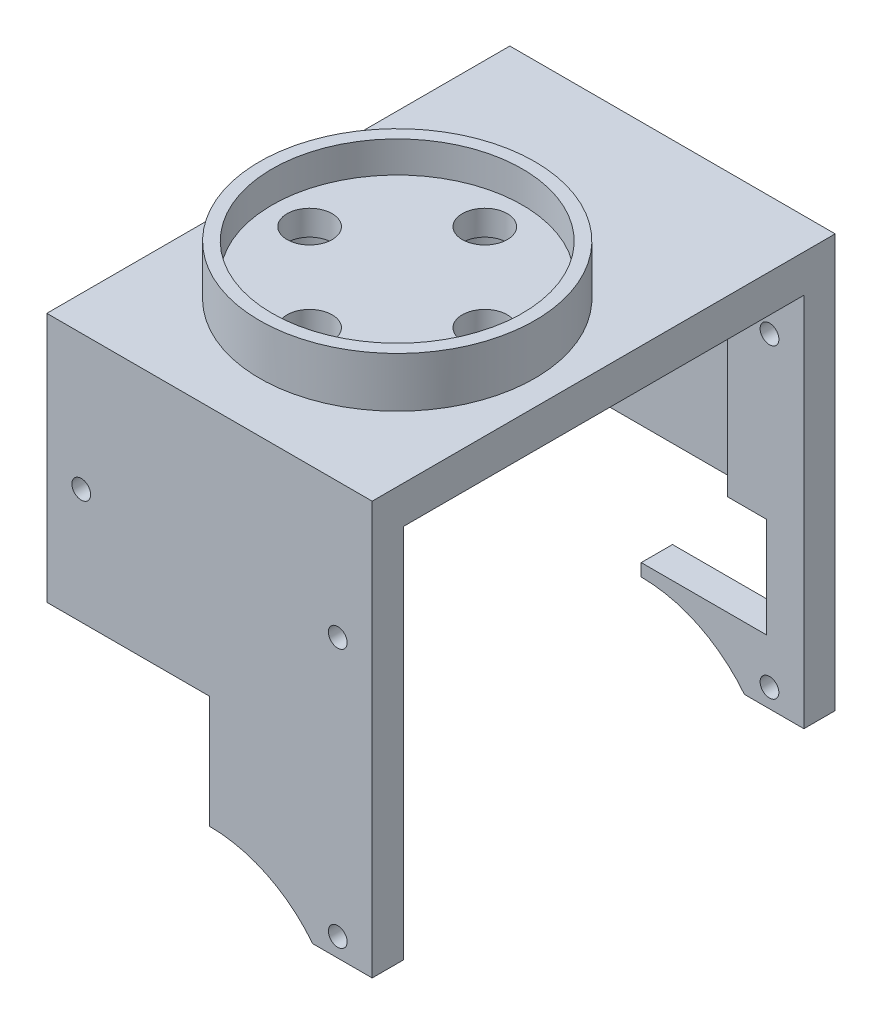
SolidWorks part; units mm, degrees
ref_plane "前视基准面" through (0, 0, 0) normal (0, 0, 1) x (1, 0, 0)
ref_plane "上视基准面" through (0, 0, 0) normal (0, 1, 0) x (1, 0, 0)
ref_plane "右视基准面" through (0, 0, 0) normal (1, 0, 0) x (0, 0, -1)
other "Configuration Table"
sketch "草图1" plane through (0, 0, 0) normal (0, 0, 1) x (1, 0, 0)
  line L1 (0, 0) -> (26, 0)
  line L2 (0, 0) -> (0, 33)
  line L3 (0, 33) -> (26, 33)
  line L4 (26, 0) -> (26, 33)
  dimension "D1" = 26
  dimension "D2" = 33
extrude "凸台-拉伸1" add sketch "草图1" along normal blind 37
sketch "草图3" plane through (0, 0, 0) normal (0, -1, 0) x (1, 0, 0)
  line L0 (0, 18.5) -> (-50000, 18.5) construction
  line L1 (0, 37) -> (0, 0) construction
  line L2 (26, 37) -> (26, 0) construction
  line L3 (0, 34.5) -> (26, 34.5)
  line L4 (0, 34.5) -> (0, 2.5)
  line L5 (0, 2.5) -> (26, 2.5)
  line L6 (26, 34.5) -> (26, 2.5)
  point P4 (0, 18.5)
  point P9 (0, 18.5)
  dimension "D1" = 32
extrude "切除-拉伸1" cut sketch "草图3" against normal offset from surface (30 mm away) 3 up to face at (13, 33, 18.5)
sketch "草图2" plane through (0, 0, 37) normal (0, 0, 1) x (1, 0, 0)
  line L0 (13, 0) -> (13, -50000) construction
  line L1 (0, 0) -> (26, 0) construction
  line L3 (2.75, 22.2) -> (23.25, 22.2) construction
  line L4 (2.75, 22.2) -> (2.75, 1.5) construction
  line L5 (2.75, 1.5) -> (23.25, 1.5) construction
  line L6 (23.25, 22.2) -> (23.25, 1.5) construction
  circle A0 centre (2.75, 1.5) radius 0.75
  circle A1 centre (23.25, 1.5) radius 0.75
  circle A2 centre (23.25, 22.2) radius 0.75
  circle A3 centre (2.75, 22.2) radius 0.75
  point P4 (13, 0)
  point P9 (13, 22.2)
  dimension "D4" = 1.5
  dimension "D5" = 1.5
  dimension "D6" = 1.5
  dimension "D7" = 1.5
  dimension "D1" = 1.5
  dimension "D2" = 20.5
  dimension "D3" = 20.7
extrude "切除-拉伸2" cut sketch "草图2" against normal up to next and the other way through all
sketch "草图4" plane through (0, 0, 0) normal (0, 0, -1) x (-1, 0, 0)
  line L1 (-23.25, 1.5) -> (-3.25, 1.5) construction
  line L2 (-23.25, 1.5) -> (-23.25, 25.95) construction
  line L3 (-23.25, 25.95) -> (-3.25, 25.95) construction
  line L4 (-3.25, 1.5) -> (-3.25, 25.95) construction
  circle A0 centre (-2.75, 1.5) radius 0.75 construction
  circle A1 centre (-23.25, 1.5) radius 0.75 construction
  circle A2 centre (-2.75, 1.5) radius 0.75
  circle A3 centre (-23.25, 1.5) radius 0.75
  circle A4 centre (-23.25, 25.95) radius 0.75
  circle A5 centre (-3.25, 25.95) radius 0.75
  dimension "D2" = 1.5
  dimension "D3" = 1.5
  dimension "D1" = 24.45
extrude "切除-拉伸3" cut sketch "草图4" against normal up to next
sketch "草图5" plane through (0, 0, 0) normal (0, -1, 0) x (1, 0, 0)
  line L0 (13, 37) -> (13, -49963) construction
  line L1 (0, 37) -> (26, 37) construction
  line L2 (0, 34.5) -> (26, 34.5) construction
  line L3 (4.5, 36) -> (21.5, 36)
  line L4 (4.5, 36) -> (4.5, 34.5)
  line L5 (4.5, 34.5) -> (21.5, 34.5)
  line L6 (21.5, 36) -> (21.5, 34.5)
  point P4 (13, 37)
  point P9 (13, 36)
  dimension "D1" = 1.5
  dimension "D2" = 17
extrude "切除-拉伸4" cut sketch "草图5" against normal blind 27
sketch "草图6" plane through (0, 0, 0) normal (0, 0, -1) x (-1, 0, 0)
  line L0 (-13, 0) -> (-13, 50000) construction
  line L1 (0, 0) -> (-26, 0) construction
  line L3 (-23, 13) -> (-3, 13)
  line L4 (-23, 13) -> (-23, 5)
  line L5 (-23, 5) -> (-3, 5)
  line L6 (-3, 13) -> (-3, 5)
  point P4 (-13, 0)
  point P9 (-13, 13)
  dimension "D1" = 5
  dimension "D2" = 8
  dimension "D3" = 20
extrude "切除-拉伸5" cut sketch "草图6" against normal up to next
sketch "草图7" plane through (0, 0, 0) normal (0, 0, -1) x (-1, 0, 0)
  line L0 (-13, 0) -> (-13, -50000) construction
  line L1 (0, 0) -> (-26, 0) construction
  line L2 (-13, 4) -> (0, 4)
  line L3 (0, 33) -> (0, 0) construction
  line L4 (-3, 13) -> (-23, 13) construction
  line L5 (-13, 4) -> (0, 4)
  line L6 (-13, 4) -> (-13, 13)
  line L7 (-13, 13) -> (0, 13)
  line L8 (0, 4) -> (0, 13)
  line L13 (0, 0) -> (0, 33)
  line L14 (0, 33) -> (-26, 33)
  line L15 (-26, 33) -> (-26, 0)
  line L16 (-26, 0) -> (0, 0)
  line L17 (0, 0) -> (0, 13)
  line L20 (-21.2462, 0) -> (0, 0)
  circle A0 centre (-13, -6.5) radius 10.5
  point P4 (-13, 0)
  line M11 (-23, 13) -> (-3, 13)
  line M12 (-3, 13) -> (-3, 5)
  line M13 (-3, 5) -> (-23, 5)
  circle M17 centre (-2.75, 1.5) radius 0.75
  line M18 (0, 0) -> (0, 33)
  line M21 (-26, 0) -> (0, 0)
  dimension "D1" = 6.5
  dimension "D2" = 21
  dimension "D3" = 0
extrude "切除-拉伸6" cut sketch "草图7" against normal through all contours L0 A0 M21 | A0 L0 L20 | A0 L20 L2 M18 M17 | L7 L6 L2 M12 M13 M18 | L6 M13 M12 M11 region at (13, 1.6294, 0) region at (3.949, 2.3453, 0) region at (12.8419, 4.5, 0) region at (8, 9, 0)
sketch "草图8" plane through (0, 13, 0) normal (0, -1, 0) x (1, 0, 0)
  line L1 (12.3977, -4.7974) -> (12.3977, 15.9697) construction
  line L3 (23, 2.5) -> (0, 2.5) construction
  line L4 (4.8977, 1) -> (19.8977, 1)
  line L5 (4.8977, 1) -> (4.8977, 2.5)
  line L6 (4.8977, 2.5) -> (19.8977, 2.5)
  line L7 (19.8977, 1) -> (19.8977, 2.5)
  point P2 (12.3977, 2.5)
  dimension "D1" = 1.5
  dimension "D2" = 15
extrude "切除-拉伸7" cut sketch "草图8" against normal blind 13
sketch "草图9" plane through (0, 33, 0) normal (0, 1, 0) x (1, 0, 0)
  line L0 (13, -37) -> (13, 49963) construction
  line L1 (26, -37) -> (0, -37) construction
  circle A0 centre (13, -22) radius 11
  circle A1 centre (13, -22) radius 10
  point P4 (13, -37)
  point P8 (13, -24.18)
  point P9 (13, -23.9135)
  dimension "D1" = 22
  dimension "D2" = 20
  dimension "D3" = 15
extrude "凸台-拉伸2" add sketch "草图9" along normal blind 4
sketch "草图12" plane through (0, 33, 0) normal (0, 1, 0) x (1, 0, 0)
  circle A0 centre (13, -22) radius 10 construction
  circle A1 centre (13, -22) radius 10
extrude "凸台-拉伸3" add sketch "草图12" along normal blind 1.5
sketch "草图10" plane through (0, 33, 0) normal (0, 1, 0) x (1, 0, 0)
  circle A0 centre (13, -22) radius 7 construction
  circle A1 centre (13, -15) radius 1.8
  circle A2 centre (20, -22) radius 1.8
  circle A3 centre (13, -29) radius 1.8
  circle A4 centre (6, -22) radius 1.8
  point P14 (13, -22)
  dimension "D1" = 14
  dimension "D2" = 3.6
  dimension "D3" = 4
extrude "切除-拉伸8" cut sketch "草图10" against normal through all both and the other way through all
sketch "草图11" plane through (0, 30, 0) normal (0, -1, 0) x (1, 0, 0)
  circle A0 centre (6, 22) radius 2.8
  circle A1 centre (13, 29) radius 2.8
  circle A2 centre (20, 22) radius 2.8
  circle A3 centre (13, 15) radius 2.8
  dimension "D1" = 5.6
  dimension "D2" = 5.6
  dimension "D3" = 5.6
  dimension "D4" = 5.6
extrude "切除-拉伸9" cut sketch "草图11" against normal blind 2.5
